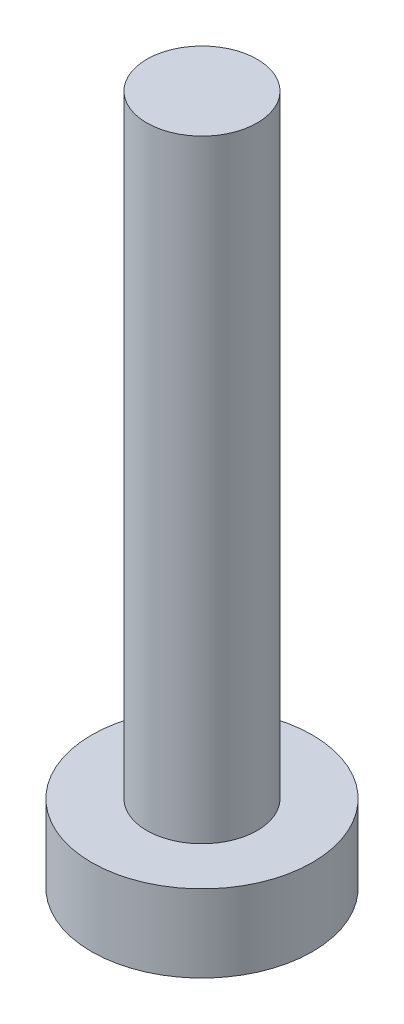
SolidWorks part; units mm, degrees
ref_plane "前视基准面" through (0, 0, 0) normal (0, 0, 1) x (1, 0, 0)
ref_plane "上视基准面" through (0, 0, 0) normal (0, 1, 0) x (1, 0, 0)
ref_plane "右视基准面" through (0, 0, 0) normal (1, 0, 0) x (0, 0, -1)
other "Configuration Table"
sketch "草图1" plane through (0, 0, 0) normal (0, 1, 0) x (1, 0, 0)
  circle A0 centre (0, 0) radius 2
  circle A1 centre (0, 0) radius 4
  point P4 (0, 0)
  dimension "D1" = 4
  dimension "D2" = 8
extrude "凸台-拉伸1" add sketch "草图1" along normal blind 2.8
extrude "凸台-拉伸3" add sketch "草图1<4>" along normal blind 25 contours A0 region at (0, 0, 0)
sketch "草图1<4>" plane through (0, 0, 0) normal (0, 1, 0) x (1, 0, 0) same geometry as "草图1"
